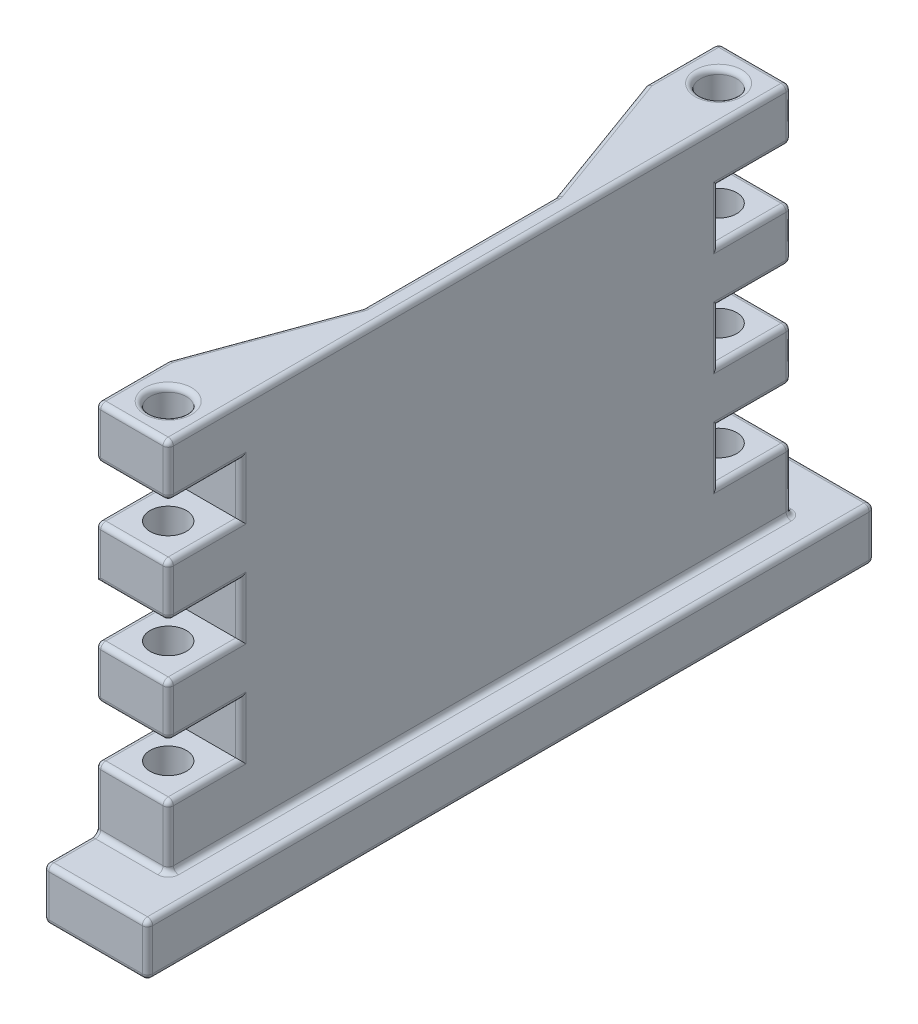
SolidWorks part; units mm, degrees
ref_plane "Front Plane" through (0, 0, 0) normal (0, 0, 1) x (1, 0, 0)
ref_plane "Top Plane" through (0, 0, 0) normal (0, 1, 0) x (1, 0, 0)
ref_plane "Right Plane" through (0, 0, 0) normal (1, 0, 0) x (0, 0, -1)
sketch "Sketch1" plane through (0, 0, 0) normal (1, 0, 0) x (0, 0, -1)
  line L1 (-15, -20.5) -> (15, -20.5)
  line L2 (-15, -4.5) -> (-15, 0.5)
  line L3 (-8, 20.5) -> (15, 20.5)
  line L4 (15, -20.5) -> (15, 20.5)
  line L5 (-15, -20.5) -> (15, 20.5) construction
  line L6 (-15, 20.5) -> (15, -20.5) construction
  line L7 (-20, -15.5) -> (-20, -20.5)
  line L8 (-20, -20.5) -> (-15, -20.5)
  line L12 (-8, 20.5) -> (-8, 15.5) construction
  line L13 (-8, 15.5) -> (-15, 15.5)
  line L14 (-8, 15.5) -> (-8, 10.5)
  line L15 (-8, 10.5) -> (-15, 10.5)
  line L16 (-8, 10.5) -> (-8, 5.5) construction
  line L17 (-8, 5.5) -> (-8, 0.5)
  line L18 (-8, 0.5) -> (-8, -4.5) construction
  line L19 (-8, -4.5) -> (-8, -9.5)
  line L20 (-8, 20.5) -> (-15, 20.5)
  line L21 (-15, 15.5) -> (-15, 20.5)
  line L22 (-8, -9.5) -> (-15, -9.5)
  line L23 (-8, -4.5) -> (-15, -4.5)
  line L24 (-8, 0.5) -> (-15, 0.5)
  line L25 (-8, 5.5) -> (-15, 5.5)
  line L26 (-15, 5.5) -> (-15, 10.5)
  line L42 (-20, -15.5) -> (-15, -15.5)
  line L43 (-15, -15.5) -> (-15, -9.5)
  point P0 (0, 0)
  dimension "D1" = 41
  dimension "D2" = 30
  dimension "D3" = 5
  dimension "D4" = 7
  dimension "D5" = 5
  dimension "D6" = 5
extrude "Boss-Extrude1" add sketch "Sketch1" along normal blind 7 contours L19 L22 L2 L7 L8 L1 L4 L3 L12 L14 L16 L17 L18 | L18 L24 L2 L23 | L25 L16 L15 L2 | L13 L12 L3 L2 region at (0, -0.6652, -0.6696)
sketch "Sketch3" plane through (7, 0, 0) normal (1, 0, 0) x (0, 0, -1)
  line L3 (15, -20.5) -> (-20, -20.5)
  line L5 (-20, -15.5) -> (-20, -20.5)
  line L6 (-20, -15.5) -> (15, -15.5)
  line L7 (15, -20.5) -> (15, 20.5) construction
  line L8 (15, -15.5) -> (15, -20.5)
sketch "Sketch7" plane through (0, -20.5, 0) normal (0, -1, 0) x (1, 0, 0)
  line L0 (0, 15) -> (7, 15)
  line L1 (0, 20) -> (0, -15) construction
  line L3 (7, 15) -> (7, 8)
  line L4 (7, 8) -> (0, 8)
  line L5 (0, 8) -> (0, 15)
  line L6 (7, 20) -> (0, 20) construction
  line L8 (7, 8) -> (0, 15) construction
  line L10 (0.6788, 9.8625) -> (3.5075, 8.238)
  line L11 (3.5075, 8.238) -> (6.3287, 9.8755)
  line L12 (6.3287, 9.8755) -> (6.3212, 13.1375)
  line L13 (6.3212, 13.1375) -> (3.4925, 14.762)
  line L14 (3.4925, 14.762) -> (0.6713, 13.1245)
  line L15 (0.6713, 13.1245) -> (0.6788, 9.8625)
  circle A0 centre (3.5, 11.5) radius 1.75
  circle A1 centre (3.5, 11.5) radius 2.825 construction
  dimension "D4" = 5.65
  dimension "D5" = 3.5
  dimension "D1" = 5
  dimension "D2" = 7
  dimension "D3" = 7
extrude "Cut-Extrude3" cut sketch "Sketch7" against normal through all both and the other way through all contours A0 region at (3.5, -20.5, 11.5)
extrude "Boss-Extrude2" add sketch "Sketch3" along normal blind 3
extrude "Cut-Extrude4" cut sketch "Sketch7<3>" against normal blind 5 and the other way through all contours L14 L15 L10 L11 L12 L13 A0 region at (0.7614, -20.5, 11.4937)
sketch "Sketch7<3>" plane through (0, -20.5, 0) normal (0, -1, 0) x (1, 0, 0) same geometry as "Sketch7"
sketch "Sketch8" plane through (0, 20.5, 0) normal (0, 1, 0) x (1, 0, 0)
  line L0 (0, -8) -> (5, 5.7374)
  line L1 (0, -15) -> (0, 15) construction
  line L2 (5, 5.7374) -> (5, 15)
  line L3 (7, 15) -> (0, 15) construction
  line L4 (0, -8) -> (0, 15)
  line L5 (0, 15) -> (5, 15)
  dimension "D1" = 2
  dimension "D2" = 7
  dimension "D3" = 200
extrude "Cut-Extrude5" cut sketch "Sketch8" against normal blind 39
mirror "Mirror2" about plane through (7, 0, -15) normal (0, 0, 1) of bodies 111 109
fillet "Fillet1" radius 0.5 87 edges at (3.5, -9.5, 15) (3.5, -15.5, 15) (0, -12.5, 15) (5, -15.5, 20) (5, -20.5, 20) (0, -18, 20) (5, -20.5, -50) (5, -15.5, -50) (0, -18, -50) (3.5, -15.5, -45) (3.5, -9.5, -45) (0, -12.5, -45) (3.5, -4.5, -45) (3.5, 0.5, -45) (0, -2, -45) (3.5, 5.5, -45) (3.5, 10.5, -45) (0, 8, -45) (3.5, 15.5, -45) (0, 18, -45) (3.5, 15.5, 15) (0, 18, 15) (3.5, 10.5, 15) (3.5, 5.5, 15) (0, 8, 15) (3.5, 0.5, 15) (3.5, -4.5, 15) (0, -2, 15) (5, 1, -5.7374) (5, 1, -24.2626) (7, -9.5, 11.5) (7, -7, 8) (7, -4.5, 11.5) (7, -2, 15) (7, 0.5, 11.5) (7, 3, 8) (7, 5.5, 11.5) (7, 8, 15) (7, 10.5, 11.5) (7, 13, 8) (7, 15.5, 11.5) (7, 18, 15) (7, 18, -45) (7, 15.5, -41.5) (7, 13, -38) (7, 10.5, -41.5) (7, 8, -45) (7, 5.5, -41.5) (7, 3, -38) (7, 0.5, -41.5) (7, -2, -45) (7, -4.5, -41.5) (7, -7, -38) (7, -9.5, -41.5) (7, -12.5, -45) (7, -15.5, -15) (7, -12.5, 15) (3.5, 20.5, -39.75) (3.5, 20.5, 9.75) (5, 20.5, -15) (2.5, 20.5, -31.1313) (0, 20.5, -41.5) (3.5, 20.5, -45) (7, 20.5, -15) (3.5, 20.5, 15) (0, 20.5, 11.5) (2.5, 20.5, 1.1313) (0, -4.5, 11.5) (0, 0.5, 11.5) (0, 10.5, 11.5) (0, 15.5, 11.5) (0, -9.5, 11.5) (0, -15.5, 17.5) (0, 15.5, -41.5) (0, 10.5, -41.5) (0, 5.5, -41.5) (0, -4.5, -41.5) (0, 0.5, -41.5) (0, -9.5, -41.5) (0, -15.5, -47.5) (0, -20.5, -15) (5, -18.5, -15) (0, -18.5, -15) (10, -18, 20) (10, -18, -50) (10, -20.5, -15) (10, -15.5, -15)
